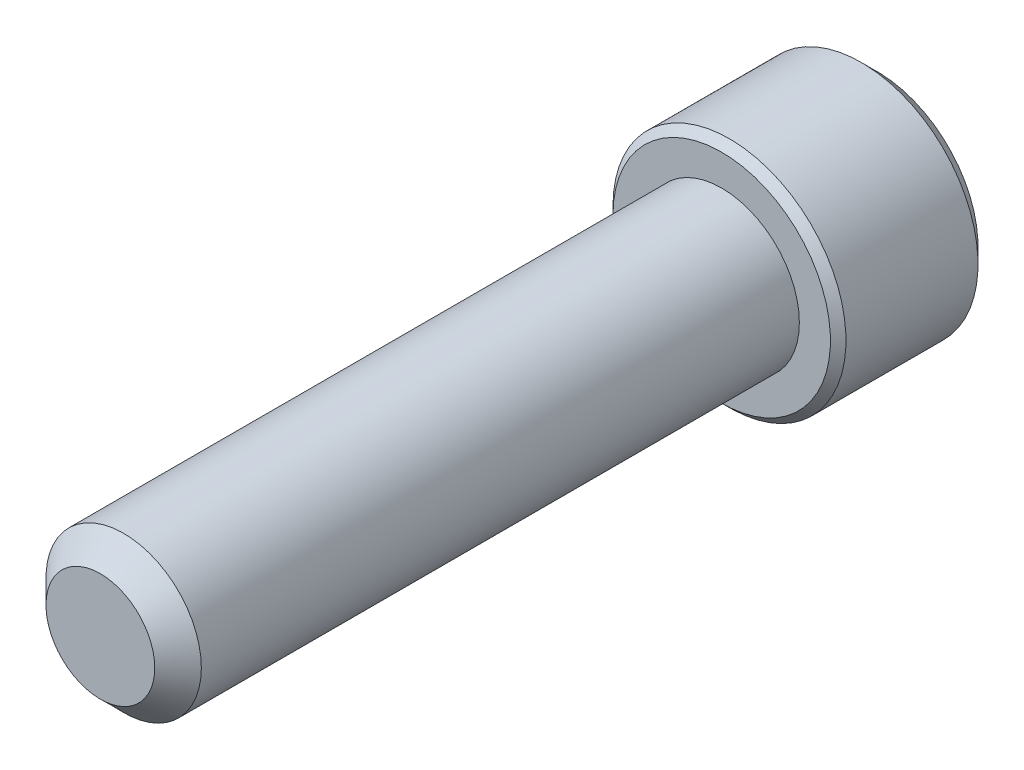
SolidWorks part; units mm, degrees
ref_plane "Front Plane" through (0, 0, 0) normal (0, 0, 1) x (1, 0, 0)
ref_plane "Top Plane" through (0, 0, 0) normal (0, 1, 0) x (1, 0, 0)
ref_plane "Right Plane" through (0, 0, 0) normal (1, 0, 0) x (0, 0, -1)
sketch "Sketch1" plane through (0, 0, 0) normal (0, 0, 1) x (1, 0, 0)
  line L0 (0, 3.175) -> (0, -3.175) construction
  circle A0 centre (0, 0) radius 3.175
  dimension "OD" = 6.35
extrude "Extrude1" add sketch "Sketch1" against normal blind 25.4
sketch "Sketch2" plane through (0, 0, 0) normal (0, 0, 1) x (1, 0, 0)
  circle A0 centre (0, 0) radius 3.175 construction
  circle A1 centre (0, 0) radius 3.175
curve "Helix/Spiral1" [suppressed] pitch 1.27 height 26.67 turns 21 parameters "pitch"=1.27
chamfer "Chamfer3" distance 0.9525 angle 45 1 edges at (3.175, 0, 0)
sketch "Sketch3" plane through (0, 0, 0) normal (1, 0, 0) x (0, 0, -1)
  line L0 (-1.1113, 3.175) -> (-0.635, 2.3501)
  line L1 (-0.635, 2.3501) -> (-0.4763, 2.3501)
  line L2 (-0.4763, 2.3501) -> (0, 3.175)
  line L3 (-1.1113, 3.175) -> (0, 3.175)
  line L4 (-0.5556, 3.175) -> (-0.5556, 2.3501) construction
  line L5 (-0.8731, 2.7626) -> (-0.2381, 2.7626) construction
  line L6 (0, 3.175) -> (0, -3.175) construction
  dimension "D1" = 0.1588
  dimension "D2" = 0.635
  dimension "D3" = 60
sweep "Cut-Sweep1" [suppressed] cut profiles "Sketch3" path "Helix/Spiral1"
sketch "Sketch6" plane through (0, 0, -25.4) normal (0, 0, -1) x (-1, 0, 0)
  circle A0 centre (0, 0) radius 4.7625
  dimension "head dia" = 9.525
extrude "Extrude2" add sketch "Sketch6" along normal blind 6.35
sketch "Sketch7" plane through (0, 0, -31.75) normal (0, 0, -1) x (-1, 0, 0)
  line L1 (0, 2.7496) -> (-2.3813, 1.3748)
  line L2 (-2.3813, 1.3748) -> (-2.3813, -1.3748)
  line L3 (-2.3813, -1.3748) -> (0, -2.7496)
  line L4 (0, -2.7496) -> (2.3813, -1.3748)
  line L5 (2.3813, -1.3748) -> (2.3813, 1.3748)
  line L6 (2.3813, 1.3748) -> (0, 2.7496)
  circle A0 centre (0, 0) radius 2.3813 construction
  dimension "hex dia" = 4.7625
extrude "Cut-Extrude1" cut sketch "Sketch7" against normal blind 3.5719
sketch "Sketch8" plane through (0, 0, -31.75) normal (0, 0, -1) x (-1, 0, 0)
  circle A0 centre (0, 0) radius 2.7496
extrude "Cut-Extrude2" cut sketch "Sketch8" against normal blind 0.635 draft 45
chamfer "Chamfer1" distance 0.635 angle 45 1 edges at (-4.7625, 0, -31.75)
chamfer "Chamfer2" distance 0.3175 angle 45 1 edges at (-4.7625, 0, -25.4)
sketch "Sketch9" plane through (0, 0, 0) normal (1, 0, 0) x (0, 0, -1)
  line L0 (0, 3.175) -> (0, -3.175) construction
  line L1 (6.985, 3.175) -> (6.985, -3.175) construction
  line L2 (25.4, 4.7625) -> (25.4, -4.7625) construction
  line L3 (31.75, 4.7625) -> (31.75, -4.7625) construction
  line L4 (31.75, 0) -> (0, 0) construction
  dimension "D1" = 6.985
  dimension "D2" = 6.35
  dimension "D3" = 9.525
  dimension "D4" = 25.4
equation "\"D3@Helix/Spiral1\" = \"screw length@Extrude1\"+\"pitch@Helix/Spiral1\""
equation "\"D1@Sketch3\" = \"pitch@Helix/Spiral1\"*.125"
equation "\"D2@Sketch3\" = \"pitch@Helix/Spiral1\"*.5"
equation "\"D1@Cut-Extrude1\" = \"hex dia@Sketch7\"*.75"
equation "\"D1@Chamfer1\" = \"head depth@Extrude2\"/10"
equation "\"D1@Sketch9\" = \"pitch@Helix/Spiral1\"*5.5"
equation "\"D1@Chamfer2\" = \"D1@Chamfer1\"/2"
equation "\"D1@Cut-Extrude2\" = \"D1@Chamfer2\"*2"
equation "\"D1@Chamfer3\" = \"pitch@Helix/Spiral1\"*.750"
equation "\"D2@Sketch9\" = \"head depth@Extrude2\""
equation "\"D3@Sketch9\" = \"head dia@Sketch6\""
equation "\"D4@Sketch9\" = \"screw length@Extrude1\""
